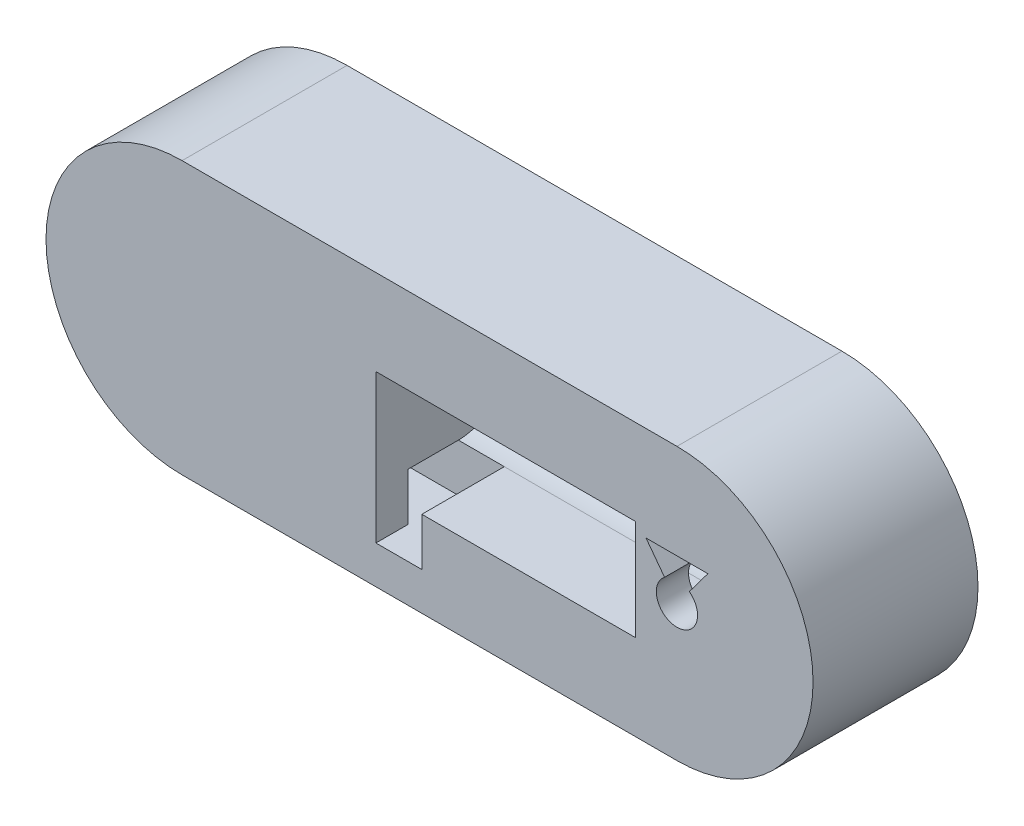
SolidWorks part; units mm, degrees
note: The reader was unsure of these and kept them because the rebuilt part matched: shared geometry of "Croquis1<4>".
ref_plane "Alzado" through (0, 0, 0) normal (0, 0, 1) x (1, 0, 0)
ref_plane "Planta" through (0, 0, 0) normal (0, 1, 0) x (1, 0, 0)
ref_plane "Vista lateral" through (0, 0, 0) normal (1, 0, 0) x (0, 0, -1)
sketch "Croquis1" plane through (0, 0, 0) normal (0, 0, 1) x (1, 0, 0)
  line L0 (-43.0271, -33) -> (76.9729, -33)
  line L1 (-43.0271, 33) -> (76.9729, 33)
  line L2 (-39.2341, 3.2577) -> (-39.2341, -3.2577)
  line L3 (69.4729, 10) -> (73.9729, 4)
  line L4 (73.9729, 4) -> (79.9729, 4)
  line L5 (79.9729, 4) -> (84.4729, 10)
  line L6 (84.4729, 10) -> (69.4729, 10)
  circle A0 centre (-43.0271, 0) radius 33
  circle A1 centre (76.9729, 0) radius 33
  circle A2 centre (-43.0271, 0) radius 5
  circle A3 centre (76.9729, 0) radius 5
  point P17 (69.5934, 10.43)
  dimension "D2" = 10
  dimension "D3" = 10
  dimension "D4" = 66
  dimension "D1" = 120
  dimension "D5" = 15
  dimension "D6" = 6
extrude "Saliente-Extruir1" add sketch "Croquis1" along normal blind 40 contours A0 L0 A2 | A1 L1 A0 L0 | L1 A1 A3 | A2 | L2 A2
extrude "Cortar-Extruir2" cut sketch "Croquis1<4>" along normal blind 10 contours L2 A2
sketch "Croquis1<4>" plane through (0, 0, 0) normal (0, 0, 1) x (1, 0, 0) same geometry as "Croquis1"
sketch "Croquis5" plane through (0, 0, 40) normal (0, 0, 1) x (1, 0, 0)
  line L0 (15.1104, -23.8) -> (15.1104, -12.2)
  line L1 (15.1104, -12.2) -> (66.9729, -12.2)
  line L9 (3.9729, 12.2) -> (3.9729, -23.8)
  line L10 (66.9729, -12.2) -> (66.9729, 12.2)
  line L13 (3.9729, -23.8) -> (15.1104, -23.8)
  line L14 (66.9729, 12.2) -> (3.9729, 12.2)
  arc A0 (76.9729, -33) -> (76.9729, 33) centre (76.9729, 0) ccw construction
  arc A1 (76.9729, -33) -> (76.9729, 33) centre (76.9729, 0) ccw
  circle A2 centre (76.9729, 0) radius 5 construction
  circle A3 centre (76.9729, 0) radius 5
  point P2 (66.9729, 0)
  dimension "D2" = 10
  dimension "D3" = 63
  dimension "D4" = 24.4
  dimension "D1" = 11.6
extrude "Cortar-Extruir4" cut sketch "Croquis5" against normal blind 20 contours L10 L14 L9 L13 L0 L1
ref_plane "Plano2" through (3.9729, 0, 0) normal (1, 0, 0) x (0, 0, -1)
sketch "Croquis6" plane through (3.9729, 0, 0) normal (1, 0, 0) x (0, 0, -1)
  line L0 (-20, 12.2) -> (-40, 12.2)
  line L1 (-20, -12.2) -> (-40, -12.2)
  line L2 (-20, -23.8) -> (-20, -12.2)
  line L4 (-40, 12.2) -> (-40, -23.8)
  line L5 (-40, -23.8) -> (-20, -23.8)
  line L6 (-20, -23.8) -> (-20, 12.2)
  line L7 (-20, 12.2) -> (-40, 12.2)
  line L8 (-40, 12.2) -> (-40, -23.8)
  line L9 (-40, -23.8) -> (-20, -23.8)
  line L11 (-20, 12.2) -> (-40, 12.2)
  line L16 (0, -33) -> (0, 33)
  line L17 (0, 33) -> (-40, 33)
  line L18 (-40, 33) -> (-40, -33)
  line L19 (-40, -33) -> (0, -33)
  line L20 (0, -33) -> (0, 33)
  line L21 (0, 33) -> (-40, 33)
  line L22 (-40, 33) -> (-40, -33)
  line L23 (-40, -33) -> (0, -33)
  circle A0 centre (-20, 0) radius 12.2
  dimension "D2" = 24.4
  dimension "D3" = 0
  dimension "D1" = 0
extrude "Cortar-Extruir6" cut sketch "Croquis6" along direction (1, 0, 0) on the side of the normal up to surface (63 mm away) contours A0 | A0 L0 L8 L1
sketch "Croquis7" plane through (66.9729, 0, 0) normal (-1, 0, 0) x (0, 0, 1)
  line L1 (40, -12.2) -> (40.0638, -12.2)
  line L3 (20, -12.2) -> (7.8, -12.2)
  line L4 (20, -12.2) -> (20, 12.2) construction
  line L5 (20, 12.2) -> (7.8, 12.2)
  line L9 (40, 12.2) -> (40.0638, 12.2)
  line L11 (7.8, -12.2) -> (7.8, 12.2)
  line L12 (40, -12.2) -> (40, 12.2)
  line L13 (40, 12.2) -> (20, 12.2)
  line L16 (20, -12.2) -> (40, -12.2)
  line L17 (40, -12.2) -> (40, 12.2)
  line L22 (40, 12.2) -> (20, 12.2)
  line L26 (7.8, -12.2) -> (32.2, -12.2)
  line L27 (7.8, -12.2) -> (7.8, 12.2)
  line L28 (7.8, 12.2) -> (32.2, 12.2)
  line L29 (32.2, -12.2) -> (32.2, 12.2)
  line L31 (20, -12.2) -> (40, -12.2)
  circle A0 centre (20, 0) radius 12.2 construction
  arc A1 (20, 12.2) -> (20, -12.2) centre (20, 0) ccw
  arc A7 (20, 12.2) -> (20, -12.2) centre (20, 0) ccw
  dimension "D1" = 0
extrude "Cortar-Extruir9" cut sketch "Croquis7" against normal blind 30
sketch "Croquis8" plane through (3.9729, 0, 0) normal (1, 0, 0) x (0, 0, -1)
  line L0 (-32.2, -12.2) -> (-32.2, -23.8)
  line L5 (-40, -12.2) -> (-32.2, -12.2)
  line L6 (-40, 12.2) -> (-40, -12.2)
  line L8 (-40, -12.2) -> (-40, -23.8)
  line L9 (-20, -12.2) -> (-40, -12.2)
  line L10 (-20, -23.8) -> (-20, -12.2)
  line L11 (-40, -23.8) -> (-20, -23.8)
  line L12 (-40, -12.2) -> (-40, -23.8)
  line L13 (-20, -12.2) -> (-32.2, -12.2)
  line L14 (-20, -23.8) -> (-20, -12.2)
  line L15 (-40, -23.8) -> (-20, -23.8)
  line L18 (-40, 12.2) -> (-40, -12.2)
  line L20 (-32.2, -12.2) -> (-32.2, 12.2)
  line L21 (-32.2, 12.2) -> (-40, 12.2)
  line L23 (-32.2, 12.2) -> (-40, 12.2)
  line M10 (-40, -23.8) -> (-20, -23.8)
  line M11 (-20, -23.8) -> (-20, -12.2)
  dimension "D1" = 0
  dimension "D2" = 0
extrude "Cortar-Extruir10" cut sketch "Croquis8" against normal blind 50 contours L13 L0 M11 M10
sketch "Croquis9" plane through (0, 0, 0) normal (0, 0, -1) x (-1, 0, 0)
  line L0 (34.4271, -23.8) -> (34.4271, -12.2)
  line L7 (46.0271, -12.2) -> (-3.9729, -12.2)
  line L8 (-3.9729, -12.2) -> (-3.9729, -23.8)
  line L9 (-3.9729, -23.8) -> (46.0271, -23.8)
  line L10 (46.0271, -23.8) -> (46.0271, -12.2)
  line L13 (34.4271, -23.8) -> (46.0271, -23.8)
  line L14 (46.0271, -23.8) -> (46.0271, -12.2)
  line L16 (46.0271, -12.2) -> (-3.9729, -12.2)
  dimension "D2" = 0
extrude "Cortar-Extruir11" cut sketch "Croquis9" against normal up to next contours L14 L16 L0 L13
chamfer "Chaflán1" distance 10 angle 45 1 edges at (-46.0271, -18, 0)
